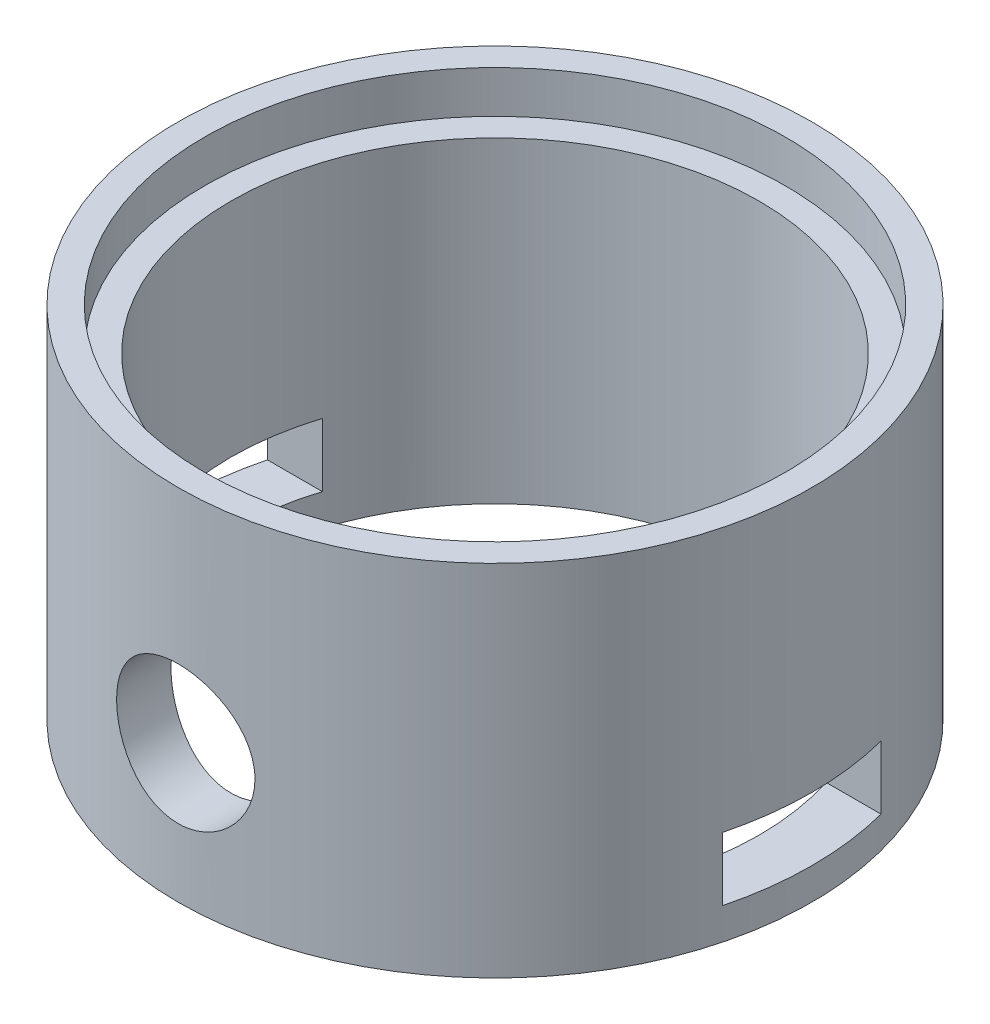
SolidWorks part; units mm, degrees
ref_plane "Front Plane" through (0, 0, 0) normal (0, 0, 1) x (1, 0, 0)
ref_plane "Top Plane" through (0, 0, 0) normal (0, 1, 0) x (1, 0, 0)
ref_plane "Right Plane" through (0, 0, 0) normal (1, 0, 0) x (0, 0, -1)
sketch "Sketch1" plane through (0, 0, 0) normal (0, 1, 0) x (1, 0, 0)
  circle A0 centre (0, 0) radius 22.5
extrude "Boss-Extrude2" add sketch "Sketch1" along normal blind 20
sketch "Sketch3" plane through (0, 20, 0) normal (0, 1, 0) x (1, 0, 0)
  circle A0 centre (0, 0) radius 20
extrude "Cut-Extrude1" cut sketch "Sketch3" against normal blind 3
sketch "Sketch7" plane through (0, 0, 0) normal (0, 0, 1) x (1, 0, 0)
  line L0 (20, 17) -> (-20, 17) construction
  line L1 (-27.3484, 12) -> (27.6799, 12)
  line L2 (-27.3484, 12) -> (-27.3484, -3.3039)
  line L3 (-27.3484, -3.3039) -> (27.6799, -3.3039)
  line L4 (27.6799, 12) -> (27.6799, -3.3039)
  dimension "D1" = 5
extrude "Cut-Extrude5" cut sketch "Sketch7" against normal mid plane 80
sketch "Sketch8" plane through (0, 12, 0) normal (0, -1, 0) x (1, 0, 0)
  circle A0 centre (0, 0) radius 22.5
  circle A1 centre (0, 0) radius 20
extrude "Boss-Extrude3" add sketch "Sketch8" along normal blind 25
sketch "Sketch9" plane through (0, 0, 0) normal (1, 0, 0) x (0, 0, -1)
  line L0 (0, 18.15) -> (0, -18.15) construction
  line L1 (-7.5, -4) -> (7.5, -4)
  line L2 (-7.5, -4) -> (-7.5, -10)
  line L3 (-7.5, -10) -> (7.5, -10)
  line L4 (7.5, -4) -> (7.5, -10)
  line L5 (-20, -13) -> (20, -13) construction
  dimension "D1" = 15
  dimension "D2" = 7.5
  dimension "D3" = 3
  dimension "D4" = 6
extrude "Cut-Extrude6" cut sketch "Sketch9" against normal mid plane 70
sketch "Sketch17" plane through (0, 0, 0) normal (1, 0, 0) x (0, 0, -1)
  line L0 (-20, 0) -> (-18, 0)
  line L1 (24.75, 0) -> (-24.75, 0) construction
  line L3 (-10, 8) -> (-10, 12)
  line L5 (-20, 12) -> (-20, -13) construction
  arc A0 (-10, 8) -> (-18, 0) centre (-18, 8) cw
  point P12 (-10, 0)
  dimension "D1" = 8
  dimension "D2" = 10
sketch "Sketch18" plane through (0, 12, 0) normal (0, 1, 0) x (1, 0, 0)
  line L0 (-18.15, 0) -> (18.15, 0) construction
  circle A0 centre (0, -10) radius 7.5
  dimension "D1" = 15
  dimension "D2" = 10
sweep "Sweep1" add profiles "Sketch18" path "Sketch17"
sketch "Sketch20" plane through (0, 17, 0) normal (0, 1, 0) x (1, 0, 0)
  circle A0 centre (0, -10) radius 5
sketch "Sketch21" plane through (0, 0, 0) normal (1, 0, 0) x (0, 0, -1)
  line L0 (-10, 17) -> (-10, 8)
  line L1 (-5, 17) -> (-15, 17) construction
  line L2 (24.75, 0) -> (-24.75, 0) construction
  line L3 (-18, 0) -> (-22.5, 0)
  line L4 (-22.5, 20) -> (-22.5, -13) construction
  arc A0 (-18, 0) -> (-10, 8) centre (-18, 8) ccw
  point P11 (-10, 0)
  dimension "D1" = 8
sweep "Cut-Sweep1" cut profiles "Sketch20" path "Sketch21"
ref_plane "Plane8" through (0, 0, 23) normal (0, 0, 1) x (1, 0, 0)
sketch "Sketch22" plane through (0, 0, 23) normal (0, 0, 1) x (1, 0, 0)
  circle A0 centre (0, 0) radius 6.55
extrude "Cut-Extrude10" cut sketch "Sketch22" against normal blind 6
ref_plane "Plane9" through (0, 0, 20) normal (0, 0, 1) x (1, 0, 0)
sketch "Sketch23" plane through (0, 0, 20) normal (0, 0, 1) x (1, 0, 0)
  circle A0 centre (0, 0) radius 6.55
  circle A1 centre (0, 0) radius 8
extrude "Boss-Extrude4" add sketch "Sketch23" along normal blind 10
sketch "Sketch24" plane through (0, 17, 0) normal (0, 1, 0) x (1, 0, 0)
  line L0 (-18.7, 0) -> (18.7, 0) construction
  line L1 (0, -18.7) -> (0, 18.7) construction
  circle A0 centre (0.75, 0) radius 0.5
  circle A1 centre (-0.75, 0) radius 0.5
  circle A2 centre (-17.5, 0) radius 0.6
  circle A3 centre (17.5, 0) radius 0.6
  point P13 (-0.25, 0)
  point P14 (0.25, 0)
  dimension "D1" = 0.75
  dimension "D2" = 0.75
  dimension "D3" = 17.5
  dimension "D4" = 17.5
  dimension "D5" = 1.5
  dimension "D6" = 0.5
  dimension "D7" = 1
  dimension "D8" = 1
extrude "Cut-Extrude11" cut sketch "Sketch24" against normal through all
sketch "Sketch25" plane through (0, 20, 0) normal (0, 1, 0) x (1, 0, 0)
  circle A0 centre (0, 0) radius 30
  circle A1 centre (0, 0) radius 22.5
extrude "Boss-Extrude9" add sketch "Sketch25" against normal blind 33
sketch "Sketch27" plane through (0, 0, 17) normal (0, 0, 1) x (1, 0, 0)
  circle A0 centre (0, 0) radius 6.55
ref_plane "Plane10" through (0, -6.55, 30) normal (-1, 0, 0) x (0, 0, 1)
extrude "Cut-Extrude12" cut sketch "Sketch27" along normal blind 15 contours A0
sketch "Sketch30" plane through (0, 20, 0) normal (0, 1, 0) x (1, 0, 0)
  circle A0 centre (0, 0) radius 25
  circle A1 centre (0, 0) radius 20
extrude "Cut-Extrude17" cut sketch "Sketch30" against normal blind 3
sketch "Sketch31" plane through (0, 20, 0) normal (0, 1, 0) x (1, 0, 0)
  circle A0 centre (0, 0) radius 27.5
extrude "Cut-Extrude18" cut sketch "Sketch31" against normal blind 3
sketch "Sketch32" plane through (0, 17, 0) normal (0, 1, 0) x (1, 0, 0)
  circle A0 centre (0, 0) radius 25
  circle A1 centre (25, 0) radius 1.5
  circle A2 centre (0, 25) radius 1.5
  circle A3 centre (-25, 0) radius 1.5
  circle A4 centre (0, -25) radius 1.5
sketch "Sketch35" plane through (0, 20, 0) normal (0, 1, 0) x (1, 0, 0)
  circle A0 centre (0, 0) radius 30
  circle A1 centre (0, 0) radius 27.5
extrude "Boss-Extrude11" add sketch "Sketch35" along normal blind 1
sketch "Sketch37" plane through (0, 0, 0) normal (1, 0, 0) x (0, 0, -1)
  line L1 (-7.5, -4) -> (7.5, -4)
  line L2 (-7.5, -4) -> (-7.5, -10)
  line L3 (-7.5, -10) -> (7.5, -10)
  line L4 (7.5, -4) -> (7.5, -10)
extrude "Cut-Extrude20" cut sketch "Sketch37" against normal blind 36 and the other way blind 35
sketch "Sketch39" plane through (0, -13, 0) normal (0, -1, 0) x (1, 0, 0)
  circle A0 centre (0, 0) radius 20
  circle A1 centre (0, 0) radius 25
extrude "Cut-Extrude21" cut sketch "Sketch39" against normal blind 23
sketch "Sketch40" plane through (0, 0, 23) normal (0, 0, 1) x (1, 0, 0)
  circle A0 centre (0, 0) radius 8
  circle A1 centre (0, 0) radius 6.55
extrude "Boss-Extrude12" add sketch "Sketch40" against normal blind 7
sketch "Sketch41" plane through (0, 0, 23) normal (0, 0, 1) x (1, 0, 0)
  circle A0 centre (0, 0) radius 8
  circle A1 centre (0, 0) radius 6.55
extrude "Boss-Extrude13" add sketch "Sketch41" along normal blind 12
sketch "Sketch44" plane through (0, 17, 0) normal (0, 1, 0) x (1, 0, 0)
  circle A0 centre (0, 0) radius 25
extrude "Cut-Extrude23" cut sketch "Sketch44" against normal blind 29
sketch "Sketch45" plane through (0, 21, 0) normal (0, 1, 0) x (1, 0, 0)
  circle A0 centre (0, 0) radius 40.753
  circle A1 centre (0, 0) radius 30
extrude "Cut-Extrude24" cut sketch "Sketch45" against normal blind 62
